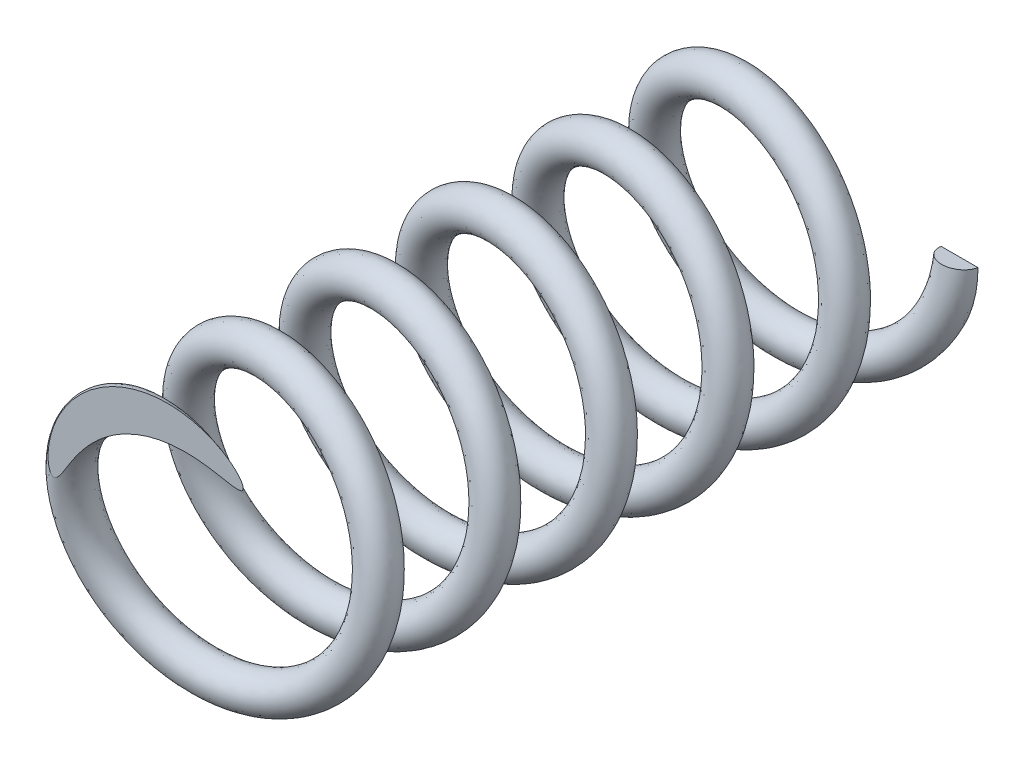
SolidWorks part; units mm, degrees
material "Alloy Steel"
ref_plane "Front Plane" through (0, 0, 0) normal (0, 0, 1) x (1, 0, 0)
ref_plane "Top Plane" through (0, 0, 0) normal (0, 1, 0) x (1, 0, 0)
ref_plane "Right Plane" through (0, 0, 0) normal (1, 0, 0) x (0, 0, -1)
ref_plane "Plane1" through (0, 0, 0) normal (0, 0, 1) x (1, 0, 0)
ref_plane "Plane2" through (0, 0, 108) normal (0, 0, -1) x (-1, 0, 0)
sketch "Sketch77" plane through (0, 0, 0) normal (0, 1, 0) x (1, 0, 0)
  line L0 (0, 0) -> (0, -108)
  line L1 (6, -108) -> (-6, -108) construction
  dimension "D1" = 108
ref_plane "Plane4" through (0, 0, 0) normal (0, 0, 1) x (1, 0, 0)
sketch "Sketch80" plane through (0, 0, 0) normal (0, 0, 1) x (1, 0, 0)
  circle A0 centre (0, 0) radius 20
  dimension "D1" = 40
curve "Helix/Spiral2" pitch 19 height 133 radius 20 left hand yes centre (0, 0, 0) axis (0, 0, 1) start towards (1, 0, 0)
ref_plane "Plane5" through (20, 0, 0) normal (0, -0.9888, 0.1495) x (-1, 0, 0)
sketch "Sketch83" plane through (20, 0, 0) normal (0, -0.9888, 0.1495) x (-1, 0, 0)
  circle A0 centre (0, 0) radius 3
  point P0 (0, 0)
  dimension "D1" = 6
sweep "Sweep2" add profiles "Sketch83" path "Helix/Spiral2"
sketch "Sketch85" plane through (0, 0, 0) normal (0, 0, 1) x (1, 0, 0)
  line L1 (-35, 35) -> (35, 35)
  line L2 (-35, 35) -> (-35, -35)
  line L3 (-35, -35) -> (35, -35)
  line L4 (35, 35) -> (35, -35)
  line L5 (-35, 35) -> (35, -35) construction
  line L6 (-35, -35) -> (35, 35) construction
  point P0 (0, 0)
  dimension "D1" = 70
  dimension "D2" = 70
extrude "Cut-Extrude3" cut sketch "Sketch85" against normal up to next
sketch "Sketch86" plane through (0, 0, 108) normal (0, 0, -1) x (-1, 0, 0)
  line L1 (35, -35) -> (-35, -35)
  line L2 (35, -35) -> (35, 35)
  line L3 (35, 35) -> (-35, 35)
  line L4 (-35, -35) -> (-35, 35)
  line L5 (35, -35) -> (-35, 35) construction
  line L6 (35, 35) -> (-35, -35) construction
  point P0 (0, 0)
  dimension "D1" = 70
  dimension "D2" = 70
extrude "Cut-Extrude4" cut sketch "Sketch86" against normal up to next
equation "\"wireDiameter\"= 6"
equation "\"D1@Sketch83\"=\"wireDiameter\""
equation "\"meanDiameter\"= 40"
equation "\"D1@Sketch80\"=\"meanDiameter\""
